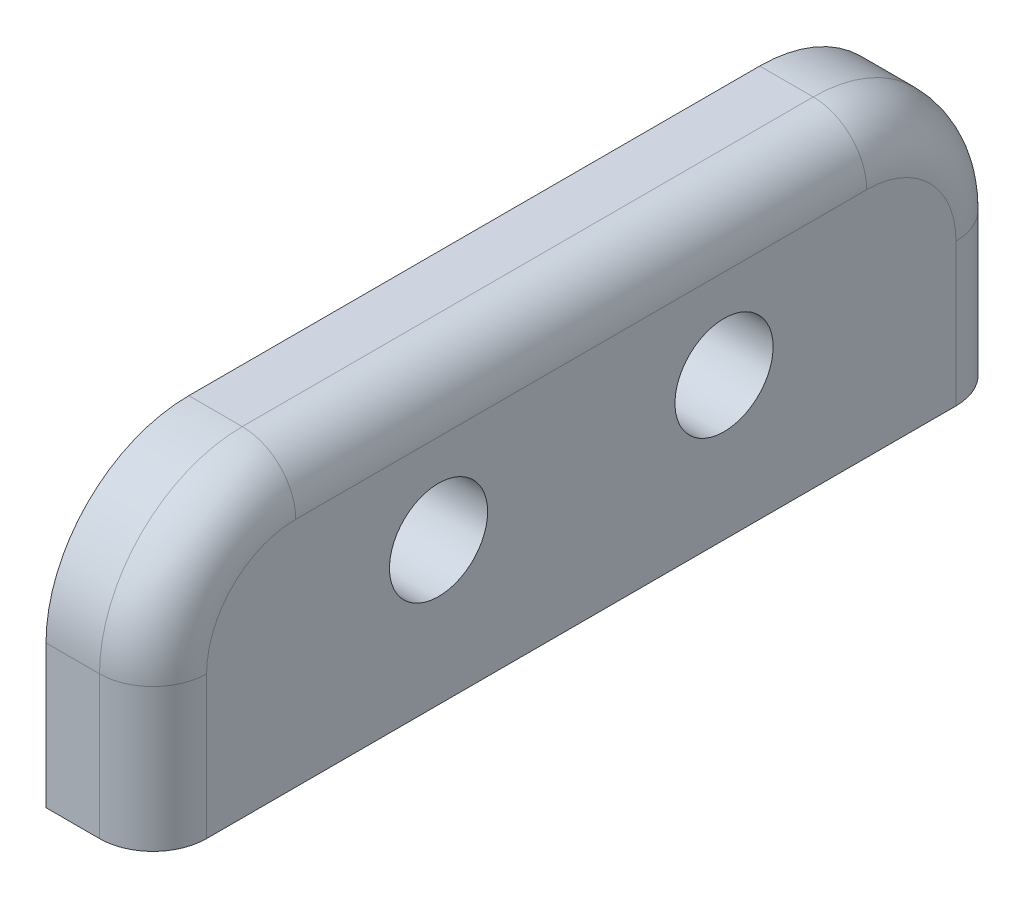
SolidWorks part; units mm, degrees
ref_plane "Front Plane" through (0, 0, 0) normal (0, 0, 1) x (1, 0, 0)
ref_plane "Top Plane" through (0, 0, 0) normal (0, 1, 0) x (1, 0, 0)
ref_plane "Right Plane" through (0, 0, 0) normal (1, 0, 0) x (0, 0, -1)
sketch "Sketch1" plane through (0, 0, 0) normal (1, 0, 0) x (0, 0, -1)
  line L0 (-8, 0) -> (8, 0) construction
  line L1 (24, -8) -> (-24, -8)
  line L2 (24, -8) -> (24, 8)
  line L3 (24, 8) -> (-24, 8)
  line L4 (-24, -8) -> (-24, 8)
  line L5 (24, -8) -> (-24, 8) construction
  line L6 (24, 8) -> (-24, -8) construction
  line L7 (8, 0) -> (8, -8) construction
  circle A0 centre (-8, 0) radius 2.75
  circle A1 centre (8, 0) radius 2.75
  point P0 (0, 0)
  dimension "D5" = 5.5
  dimension "D1" = 48
  dimension "D2" = 16
  dimension "D4" = 16
extrude "Boss-Extrude1" add sketch "Sketch1" along normal blind 6
fillet "Fillet1" radius 8 2 edges at (3, 8, 24) (3, 8, -24)
fillet "Fillet2" radius 3 5 edges at (6, -4, -24) (6, 5.6569, -21.6569) (6, -4, 24) (6, 5.6569, 21.6569) (6, 8, 0)
